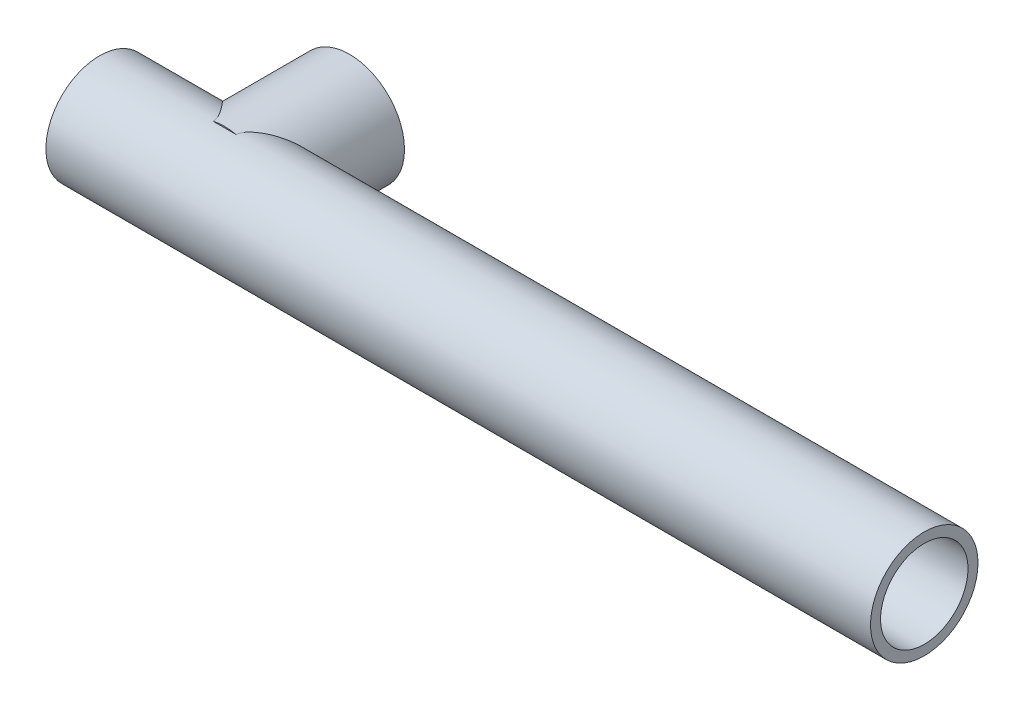
SolidWorks part; units mm, degrees
ref_plane "前视基准面" through (0, 0, 0) normal (0, 0, 1) x (1, 0, 0)
ref_plane "上视基准面" through (0, 0, 0) normal (0, 1, 0) x (1, 0, 0)
ref_plane "右视基准面" through (0, 0, 0) normal (1, 0, 0) x (0, 0, -1)
sketch "草图1" plane through (0, 0, 0) normal (1, 0, 0) x (0, 0, -1)
  circle A0 centre (0, 0) radius 8.75
  dimension "D1" = 17.5
extrude "拉伸-薄壁1" add sketch "草图1" along normal blind 165 thin thin type one direction wall 2
sketch "草图2" plane through (0, 0, 0) normal (0, 0, 1) x (1, 0, 0)
  line L0 (-1000, 0) -> (49000, 0) construction
  circle A0 centre (25, 0) radius 9
  dimension "D1" = 18
  dimension "D2" = 25
extrude "切除-拉伸1" cut sketch "草图2" against normal blind 29
sketch "草图3" plane through (0, 0, 0) normal (0, 0, 1) x (1, 0, 0)
  circle A0 centre (25, 0) radius 9 construction
  circle A1 centre (25, 0) radius 9
extrude "拉伸-薄壁2" add sketch "草图3" against normal blind 25 thin thin type one direction wall 2
sketch "草图4" plane through (0, 0, 0) normal (-1, 0, 0) x (0, 0, 1)
  arc A0 (0, 8.75) -> (0, -8.75) centre (0, 0) ccw construction
  arc A1 (0, 8.75) -> (0, -8.75) centre (0, 0) ccw
  circle A2 centre (0, 0) radius 8.75 construction
  circle A3 centre (0, 0) radius 8.75
  circle M2 centre (0, 0) radius 8.75
extrude "切除-拉伸2" cut sketch "草图4" against normal blind 169 contours M2 region at (0, 0, 0)
